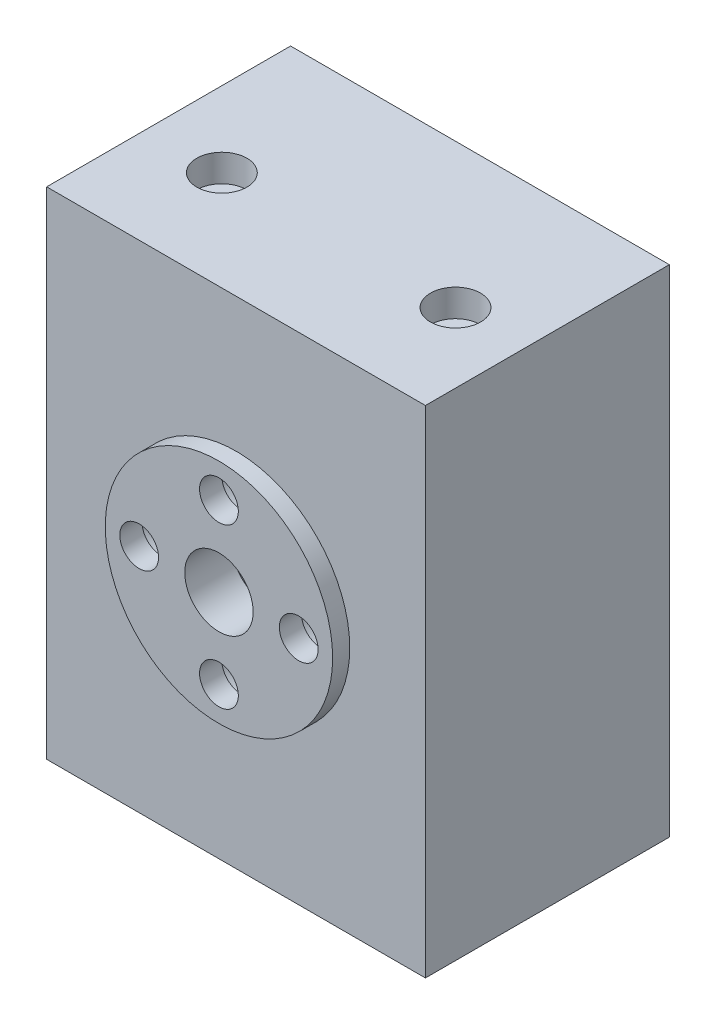
SolidWorks part; units mm, degrees
ref_plane "Front Plane" through (0, 0, 0) normal (0, 0, 1) x (1, 0, 0)
ref_plane "Top Plane" through (0, 0, 0) normal (0, 1, 0) x (1, 0, 0)
ref_plane "Right Plane" through (0, 0, 0) normal (1, 0, 0) x (0, 0, -1)
sketch "Sketch1" plane through (0, 0, 0) normal (0, 0, 1) x (1, 0, 0)
  circle A0 centre (0, 0) radius 9.975
  dimension "D1" = 19.95
extrude "Boss-Extrude1" add sketch "Sketch1" along normal blind 1.5
sketch "Sketch3" plane through (0, 0, 0) normal (0, 0, -1) x (-1, 0, 0)
  line L0 (16.615, 21.75) -> (16.615, -21.75)
  line L1 (-12.615, 17.75) -> (12.615, 17.75)
  line L2 (-12.615, 17.75) -> (-12.615, -17.75)
  line L3 (-12.615, -17.75) -> (12.615, -17.75)
  line L4 (12.615, 17.75) -> (12.615, -17.75)
  line L5 (-12.615, 17.75) -> (12.615, -17.75) construction
  line L6 (-12.615, -17.75) -> (12.615, 17.75) construction
  line L7 (-16.615, -21.75) -> (16.615, -21.75)
  line L8 (-16.615, 21.75) -> (-16.615, -21.75)
  line L9 (-16.615, 21.75) -> (16.615, 21.75)
  point P0 (0, 0)
  dimension "D1" = 35.5
  dimension "D2" = 25.23
  dimension "D3" = 4
extrude "Boss-Extrude4" add sketch "Sketch3" along normal blind 2.65 contours L2 L1 L4 L3
extrude "Boss-Extrude5" add sketch "Sketch3<5>" along normal blind 21.4
sketch "Sketch3<5>" plane through (0, 0, 0) normal (0, 0, -1) x (-1, 0, 0) same geometry as "Sketch3"
sketch "Sketch4" plane through (0, 0, -2.65) normal (0, 0, -1) x (-1, 0, 0)
  line L1 (12.615, 17.75) -> (7.415, 17.75)
  line L2 (12.615, 17.75) -> (12.615, 16.65)
  line L3 (12.615, 16.65) -> (7.415, 16.65)
  line L4 (7.415, 17.75) -> (7.415, 16.65)
  line L5 (-12.615, 17.75) -> (-7.415, 17.75)
  line L6 (-12.615, 17.75) -> (-12.615, 16.65)
  line L7 (-12.615, 16.65) -> (-7.415, 16.65)
  line L8 (-7.415, 17.75) -> (-7.415, 16.65)
  line L9 (12.615, -17.75) -> (9.415, -17.75)
  line L10 (12.615, -17.75) -> (12.615, -16.25)
  line L11 (12.615, -16.25) -> (9.415, -16.25)
  line L12 (9.415, -17.75) -> (9.415, -16.25)
  line L13 (-12.615, -17.75) -> (-9.415, -17.75)
  line L14 (-12.615, -17.75) -> (-12.615, -16)
  line L15 (-12.615, -16) -> (-9.415, -16)
  line L16 (-9.415, -17.75) -> (-9.415, -16)
  dimension "D1" = 1.1
  dimension "D2" = 5.2
  dimension "D3" = 5.2
  dimension "D4" = 1.1
  dimension "D5" = 3.2
  dimension "D6" = 1.5
  dimension "D7" = 3.2
extrude "Boss-Extrude6" add sketch "Sketch4" along normal blind 18.9 contours L2 L1 L4 L3 | L6 L5 L8 L7 | L10 L9 L12 L11 | L14 L13 L16 L15
sketch "Sketch6" plane through (0, 0, -2.65) normal (0, 0, -1) x (-1, 0, 0)
  line L1 (9.415, -17.75) -> (-9.415, -17.75)
  line L2 (9.415, -17.75) -> (9.415, -16)
  line L3 (9.415, -16) -> (-9.415, -16)
  line L4 (-9.415, -17.75) -> (-9.415, -16)
extrude "Boss-Extrude7" add sketch "Sketch6" along normal blind 5.3
sketch "Sketch2" plane through (0, 0, 1.5) normal (0, 0, 1) x (1, 0, 0)
  circle A0 centre (0, 0) radius 7 construction
  circle A1 centre (7, 0) radius 1.6
  circle A2 centre (0, -7) radius 1.6
  circle A3 centre (-7, 0) radius 1.6
  circle A4 centre (0, 7) radius 1.6
  point P14 (0, 0)
  dimension "D1" = 14
  dimension "D2" = 3.2
  dimension "D3" = 4
extrude "Cut-Extrude1" cut sketch "Sketch2" against normal blind 37
hole_wizard "CBORE for M3 Hex Socket Head Cap Screw1" positions "Sketch7" profile "Sketch8" counterbore size "M3" standard "ISO" end condition up to next
sketch "Sketch7" plane through (0, 0, -2.65) normal (0, 0, -1) x (-1, 0, 0)
  point P0 (0, 7)
  point P3 (-7, 0)
  point P6 (0, -7)
  point P9 (7, 0)
sketch "Sketch8" plane through (0, 7, -2.65) normal (1, 0, 0) x (0, 1, 0)
  line L0 (0, 0) -> (0, 4.15)
  line L1 (0, 4.15) -> (1.7, 4.15)
  line L3 (1.7, 4.15) -> (1.7, 2.2)
  line L4 (1.7, 2.2) -> (2.9, 2.2)
  line L5 (2.9, 2.2) -> (2.9, 0)
  line L7 (2.9, 0) -> (0, 0)
  line L11 (0, -6.35) -> (0, 107.95) construction
  dimension "Thru Hole Dia." = 3.4
  dimension "Thru Hole Depth" = 4.15
  dimension "C'Bore Dia." = 5.8
  dimension "C'Bore Depth" = 2.2
hole_wizard "CBORE for M2 Hex Socket Head Cap Screw1" positions "Sketch10" profile "Sketch11" counterbore size "M2" standard "ISO"
sketch "Sketch10" plane through (0, -21.75, 0) normal (0, -1, 0) x (1, 0, 0)
  point P0 (-10.005, -5.01)
  point P3 (10.495, -5.01)
sketch "Sketch11" plane through (-10.005, -21.75, -5.01) normal (1, 0, 0) x (0, 0, -1)
  line L0 (0, 0) -> (0, 7.221)
  line L1 (0, 7.221) -> (1.2, 6.5)
  line L2 (1.2, 6.5) -> (1.2, 2.4)
  line L3 (1.2, 2.4) -> (2.2, 2.4)
  line L4 (2.2, 2.4) -> (2.2, 0)
  line L5 (2.2, 0) -> (0, 0)
  line L10 (0, 7.221) -> (-1.2, 6.5) construction
  line L11 (0, -6.35) -> (0, 107.95) construction
  dimension "Hole Dia." = 2.4
  dimension "Hole Depth" = 6.5
  dimension "C'Bore Dia." = 4.4
  dimension "C'Bore Depth" = 2.4
  dimension "Drill Angle" = 118
hole_wizard "CBORE for M2 Hex Socket Head Cap Screw2" positions "Sketch12" profile "Sketch13" counterbore size "M2" standard "ISO"
sketch "Sketch12" plane through (0, 21.75, 0) normal (0, 1, 0) x (1, 0, 0)
  point P0 (-10.005, 8.76)
  point P3 (10.495, 8.76)
sketch "Sketch13" plane through (-10.005, 21.75, -8.76) normal (1, 0, 0) x (0, 0, 1)
  line L0 (0, 0) -> (0, 7.221)
  line L1 (0, 7.221) -> (1.2, 6.5)
  line L2 (1.2, 6.5) -> (1.2, 2.4)
  line L3 (1.2, 2.4) -> (2.2, 2.4)
  line L4 (2.2, 2.4) -> (2.2, 0)
  line L5 (2.2, 0) -> (0, 0)
  line L10 (0, 7.221) -> (-1.2, 6.5) construction
  line L11 (0, -6.35) -> (0, 107.95) construction
  dimension "Hole Dia." = 2.4
  dimension "Hole Depth" = 6.5
  dimension "C'Bore Dia." = 4.4
  dimension "C'Bore Depth" = 2.4
  dimension "Drill Angle" = 118
sketch "Sketch14" plane through (0, 0, -2.65) normal (0, 0, -1) x (-1, 0, 0)
  circle A0 centre (0, 0) radius 3
  dimension "D1" = 6
extrude "Cut-Extrude2" cut sketch "Sketch14" against normal blind 10
